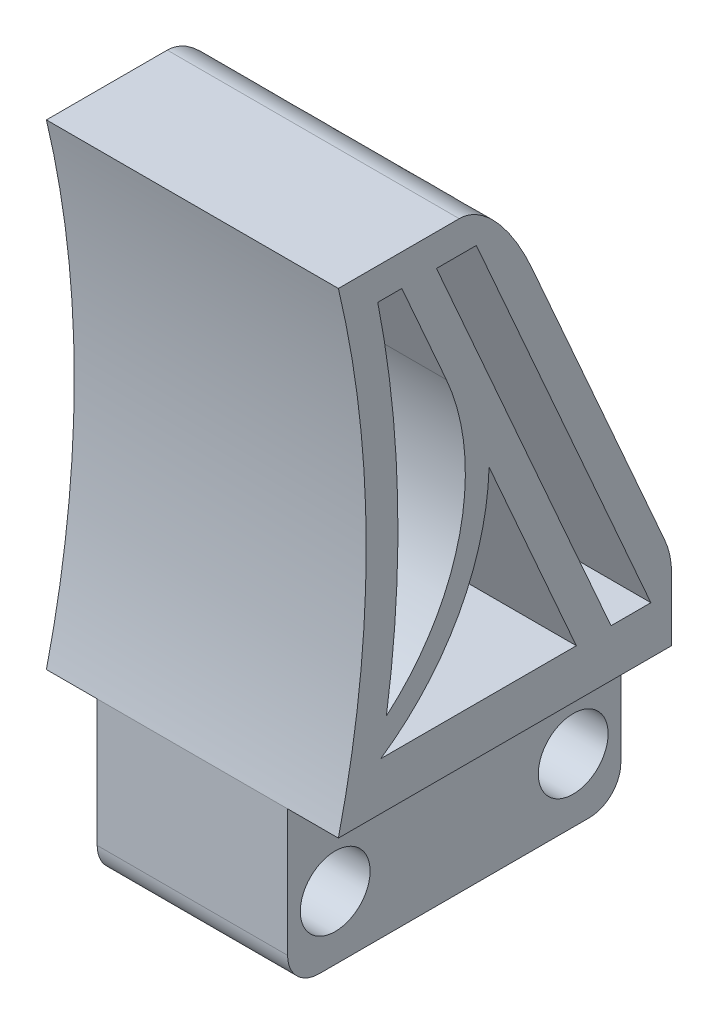
SolidWorks part; units mm, degrees
ref_plane "Front Plane" through (0, 0, 0) normal (0, 0, 1) x (1, 0, 0)
ref_plane "Top Plane" through (0, 0, 0) normal (0, 1, 0) x (1, 0, 0)
ref_plane "Right Plane" through (0, 0, 0) normal (1, 0, 0) x (0, 0, -1)
sketch "Sketch1" plane through (0, 0, 0) normal (1, 0, 0) x (0, 0, -1)
  line L0 (0, 0) -> (21, 0)
  line L4 (10, 30) -> (0, 30)
  line L5 (21, 0) -> (21, 5)
  line L6 (21, 5) -> (10, 30)
  line L7 (8.695, 28) -> (19.695, 3)
  line L9 (17.1822, 3) -> (6.1822, 28)
  line L11 (8.695, 28) -> (6.1822, 28)
  line L12 (17.1822, 3) -> (19.695, 3)
  line L13 (3.9971, 28) -> (14.9971, 3)
  line L14 (14.9971, 3) -> (2.6711, 3)
  line L15 (3.9971, 28) -> (2.4812, 28)
  arc A0 (0, 30) -> (0, 0) centre (-63.2456, 15) cw
  arc A2 (2.4812, 28) -> (2.6711, 3) centre (-63.2456, 15) cw
  arc A3 (6.8055, 21.6173) -> (3.0273, 5.1556) centre (-6.1358, 15.9231) cw
  arc A4 (9.4971, 15.5) -> (2.6711, 3) centre (-6.1358, 15.9231) cw
  point P26 (9.4971, 15.5)
  dimension "D4" = 5
  dimension "D5" = 65
  dimension "D10" = 2
  dimension "D11" = 2
  dimension "D12" = 1.5
  dimension "D1" = 21
  dimension "D2" = 30
  dimension "D3" = 10
  dimension "D6" = 2.3
  dimension "D7" = 2
  dimension "D8" = 3
  dimension "D9" = 2
extrude "Boss-Extrude1" add sketch "Sketch1" along normal blind 18.4 contours L4 A0 L0 L5 L6 A2 L15 L13 L14 L12 L9 L11 L7 | A4 L13 A3 A2 region at (0, 15, -2.1206) region at (0, 10.3649, -6.9081)
fillet "Fillet1" radius 7 1 edges at (9.2, 30, -10) second distance 5 first distance on face at (9.2, 17.5, -15.5)
fillet "Fillet2" radius 5 1 edges at (9.2, 5, -21)
sketch "Sketch2" plane through (0, 0, 0) normal (0, -1, 0) x (-1, 0, 0)
  line L6 (-18.4, 0) -> (0, 0) construction
  line L7 (-3.2, 0) -> (-15.2, 0)
  line L8 (-3.2, 0) -> (-3.2, 21)
  line L9 (-3.2, 21) -> (-15.2, 21)
  line L10 (-15.2, 0) -> (-15.2, 21)
  line L11 (-18.4, 21) -> (0, 21) construction
  point P8 (-9.2, 21)
  point P9 (-9.2, 21)
  dimension "D1" = 12
extrude "Boss-Extrude2" add sketch "Sketch2" along normal blind 10
sketch "Sketch3" plane through (15.2, 0, 0) normal (1, 0, 0) x (0, 0, -1)
  line L0 (21, -10) -> (0, -10) construction
  line L1 (3, -6) -> (18, -6) construction
  circle A0 centre (3, -6) radius 2.2
  circle A1 centre (18, -6) radius 2.2
  point P4 (10.5, -10)
  point P7 (10.5, -6)
  dimension "D1" = 15
  dimension "D2" = 4
  dimension "D3" = 4.4
extrude "Cut-Extrude1" cut sketch "Sketch3" against normal through all
fillet "Fillet3" radius 2 2 edges at (9.2, -10, 0) (9.2, -10, -21)
